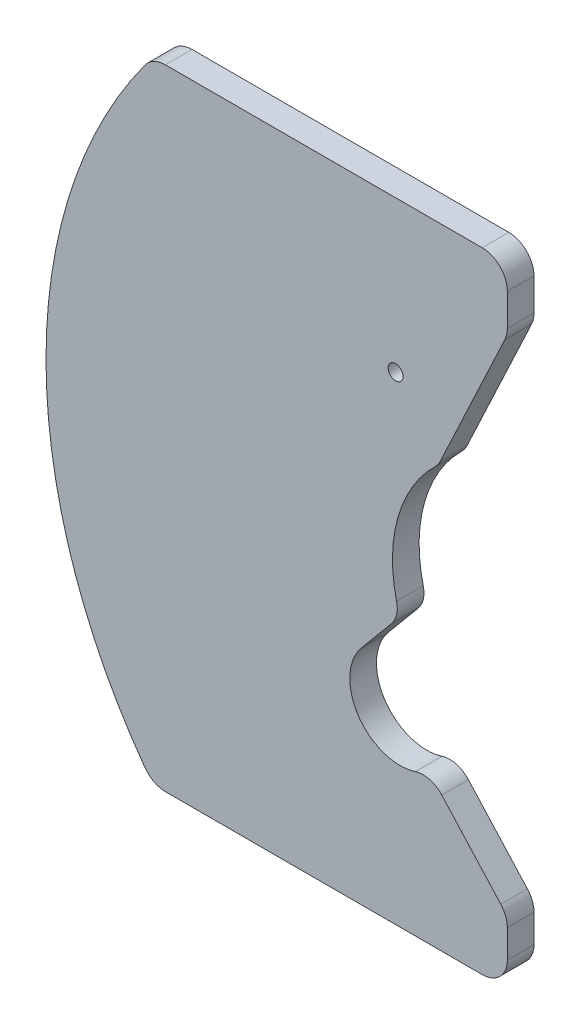
SolidWorks part; units mm, degrees
material "6061 Alloy"
ref_plane "Front Plane" through (0, 0, 0) normal (0, 0, 1) x (1, 0, 0)
ref_plane "Top Plane" through (0, 0, 0) normal (0, 1, 0) x (1, 0, 0)
ref_plane "Right Plane" through (0, 0, 0) normal (1, 0, 0) x (0, 0, -1)
sketch "Sketch1" plane through (0, 0, 0) normal (0, 0, 1) x (1, 0, 0)
  line L0 (-57.3874, 37.5) -> (-15.1374, 37.5)
  line L4 (-15.1374, -37.5) -> (-57.359, -37.5)
  line L16 (-15.1374, 37.5) -> (-15.1374, 30)
  line L19 (-15.1374, -37.5) -> (-15.1374, -30)
  line L30 (-15.1374, 30) -> (-23.3533, 12.4906)
  line L31 (-27.9226, -5.4668) -> (-32.5192, -10.9795)
  line L32 (-15.1374, -30) -> (-24.4542, -19.7261)
  arc A0 (-57.3874, 37.5) -> (-57.359, -37.5) centre (-8.5092, 0.0185) ccw
  circle A1 centre (-28.4483, 19.5) radius 0.889
  arc A6 (-23.3533, 12.4906) -> (-27.9226, -5.4668) centre (-11.8362, 0) ccw
  arc A9 (-32.5192, -10.9795) -> (-24.4542, -19.7261) centre (-27.9109, -14.8219) ccw
  dimension "D1" = 1.778
  dimension "D4" = 7.5
  dimension "D8" = 61.595
  dimension "D2" = 18
  dimension "D3" = 42.25
  dimension "D6" = 7.5
extrude "Boss-Extrude1" add sketch "Sketch1" along normal blind 3.175 contours A0 region at (-44.2153, 0.7173, 0)
fillet "Fillet1" radius 3 9 edges at (-15.1374, 37.5, 1.5875) (-57.3874, 37.5, 1.5875) (-57.359, -37.5, 1.5875) (-15.1374, -37.5, 1.5875) (-15.1374, -30, 1.5875) (-24.4542, -19.7261, 1.5875) (-27.9226, -5.4668, 1.5875) (-23.3533, 12.4906, 1.5875) (-15.1374, 30, 1.5875)
sketch "Sketch3" plane through (0, 0, 3.175) normal (0, 0, -1) x (-1, 0, 0)
  line L7 (18.1374, -37.5) -> (55.8573, -37.5)
  line L8 (18.1374, -37.5) -> (55.8573, -37.5)
  line L9 (55.8842, 37.5) -> (18.1374, 37.5)
  line L10 (55.8842, 37.5) -> (18.1374, 37.5)
  line L11 (15.4215, 29.3945) -> (23.1139, 13.0007)
  line L12 (47.4694, -37.5) -> (30.2173, -37.5)
  line L13 (45.8527, 37.5) -> (30.2173, 37.5)
  line L14 (15.4215, 29.3945) -> (23.1139, 13.0007)
  line L15 (28.9444, -6.6922) -> (32.5192, -10.9795)
  line L16 (28.9444, -6.6922) -> (32.5192, -10.9795)
  line L17 (22.9535, -21.3809) -> (15.9151, -29.1424)
  line L18 (22.9535, -21.3809) -> (15.9151, -29.1424)
  line L20 (15.1374, -31.1577) -> (15.1374, -34.5)
  line L23 (15.1374, 34.5) -> (15.1374, 30.6689)
  arc A0 (32.5973, -39.3264) -> (32.5973, 39.3264) centre (-18.6467, 0) ccw
  arc A14 (28.3352, -4.055) -> (23.7297, 12.1327) centre (11.8362, 0) ccw
  arc A15 (15.1374, -34.5) -> (18.1374, -37.5) centre (18.1374, -34.5) ccw
  arc A16 (15.1374, -34.5) -> (18.1374, -37.5) centre (18.1374, -34.5) ccw
  arc A17 (28.3352, -4.055) -> (23.7297, 12.1327) centre (11.8362, 0) ccw
  arc A18 (55.8573, -37.5) -> (58.2815, -36.2673) centre (55.8573, -34.5) ccw
  arc A19 (55.8573, -37.5) -> (58.2815, -36.2673) centre (55.8573, -34.5) ccw
  arc A20 (58.2815, -36.2673) -> (58.3098, 36.2654) centre (8.5092, 0.0185) ccw
  arc A21 (58.3098, 36.2654) -> (55.8842, 37.5) centre (55.8842, 34.5) ccw
  arc A29 (58.2815, -36.2673) -> (58.3098, 36.2654) centre (8.5092, 0.0185) ccw
  arc A31 (58.3098, 36.2654) -> (55.8842, 37.5) centre (55.8842, 34.5) ccw
  arc A32 (18.1374, 37.5) -> (15.1374, 34.5) centre (18.1374, 34.5) ccw
  arc A33 (18.1374, 37.5) -> (15.1374, 34.5) centre (18.1374, 34.5) ccw
  arc A35 (26.0875, -20.5381) -> (32.5192, -10.9795) centre (27.9109, -14.8219) ccw
  arc A36 (26.0875, -20.5381) -> (32.5192, -10.9795) centre (27.9109, -14.8219) ccw
  arc A42 (15.9151, -29.1424) -> (15.1374, -31.1577) centre (18.1374, -31.1577) ccw
  arc A43 (15.9151, -29.1424) -> (15.1374, -31.1577) centre (18.1374, -31.1577) ccw
  arc A44 (15.1374, 30.6689) -> (15.4215, 29.3945) centre (18.1374, 30.6689) ccw
  arc A45 (15.1374, 30.6689) -> (15.4215, 29.3945) centre (18.1374, 30.6689) ccw
  arc A46 (23.1139, 13.0007) -> (23.7297, 12.1327) centre (25.8298, 14.2751) ccw
  arc A47 (23.1139, 13.0007) -> (23.7297, 12.1327) centre (25.8298, 14.2751) ccw
  arc A48 (28.3352, -4.055) -> (28.9444, -6.6922) centre (31.2485, -4.771) ccw
  arc A49 (28.3352, -4.055) -> (28.9444, -6.6922) centre (31.2485, -4.771) ccw
  arc A50 (26.0875, -20.5381) -> (22.9535, -21.3809) centre (25.1758, -23.3962) ccw
  arc A51 (26.0875, -20.5381) -> (22.9535, -21.3809) centre (25.1758, -23.3962) ccw
  line M123 (18.1374, 37.5) -> (55.8842, 37.5)
  arc M124 (55.8842, 37.5) -> (58.3098, 36.2654) centre (55.8842, 34.5) cw
  arc M125 (58.3098, 36.2654) -> (58.2815, -36.2673) centre (8.5092, 0.0185) cw
  arc M126 (58.2815, -36.2673) -> (55.8573, -37.5) centre (55.8573, -34.5) cw
  line M127 (55.8573, -37.5) -> (18.1374, -37.5)
  dimension "D3" = 27.1559
  dimension "D1" = 0
extrude "Boss-Extrude3" [suppressed] add sketch "Sketch3" against normal blind 0.01 contours L8 A0 L13 M123 M124 M125 M126 M127
